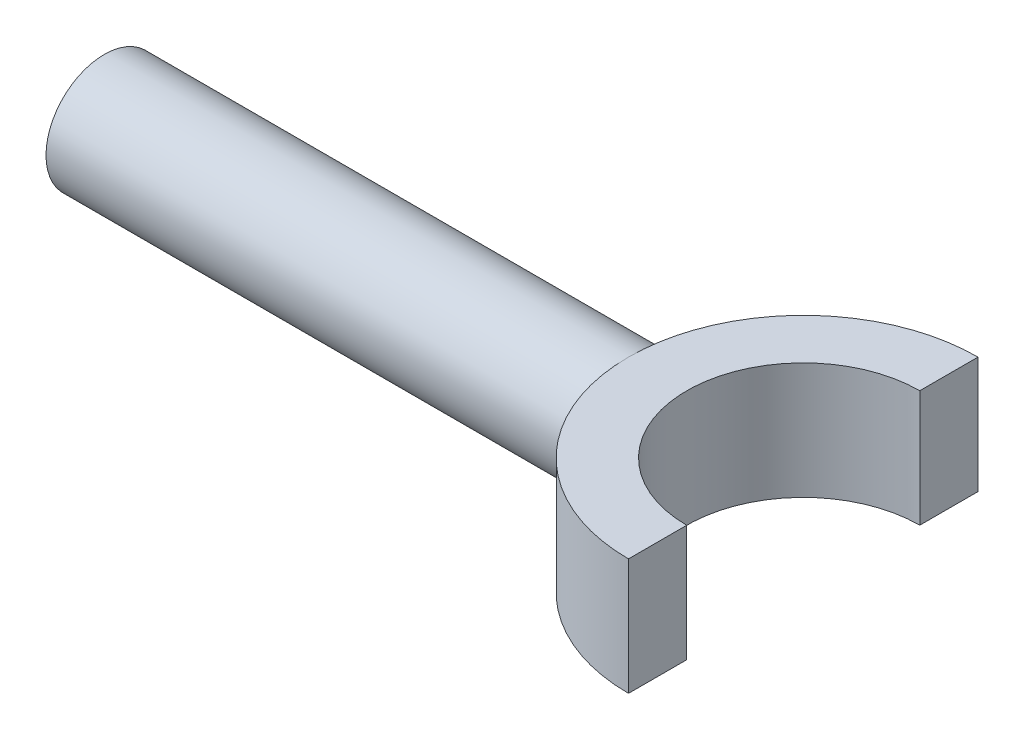
SolidWorks part; units mm, degrees
ref_plane "Front Plane" through (0, 0, 0) normal (0, 0, 1) x (1, 0, 0)
ref_plane "Top Plane" through (0, 0, 0) normal (0, 1, 0) x (1, 0, 0)
ref_plane "Right Plane" through (0, 0, 0) normal (1, 0, 0) x (0, 0, -1)
sketch "Sketch1" plane through (0, 0, 0) normal (0, 1, 0) x (1, 0, 0)
  line L0 (0, 19.05) -> (0, 12.7)
  line L1 (0, -12.7) -> (0, -19.05)
  arc A0 (0, 12.7) -> (0, -12.7) centre (0, 0) ccw
  arc A1 (0, 19.05) -> (0, -19.05) centre (0, 0) ccw
  dimension "D1" = 25.4
  dimension "D2" = 38.1
extrude "Boss-Extrude1" add sketch "Sketch1" along normal mid plane 12.7
ref_plane "Plane1" through (-76.2, 0, 0) normal (-1, 0, 0) x (0, 0, 1)
sketch "Sketch2" plane through (-76.2, 0, 0) normal (-1, 0, 0) x (0, 0, 1)
  circle A0 centre (0, 0) radius 6.35
  dimension "D1" = 12.7
extrude "Boss-Extrude2" add sketch "Sketch2" against normal up to surface (58.2395 mm away) up to face at (-9.525, 0, 0)
